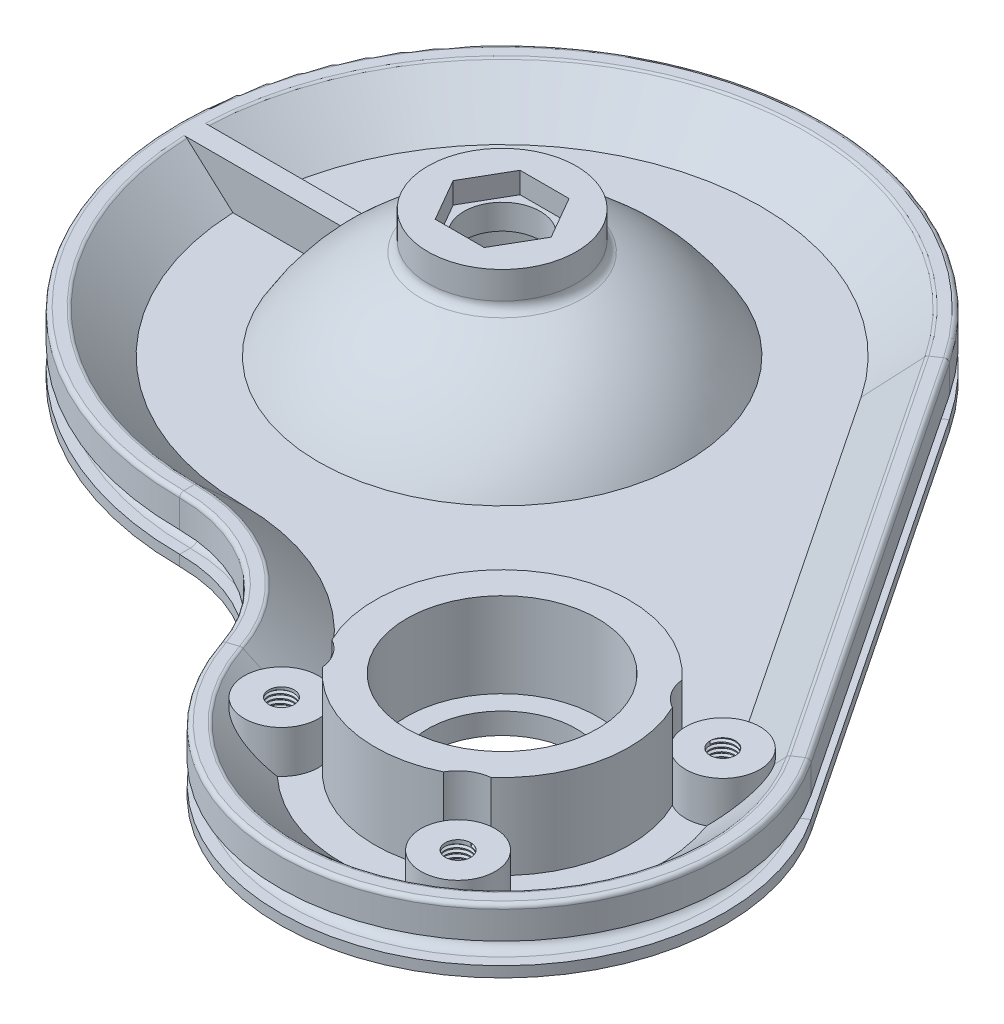
SolidWorks part; units mm, degrees
ref_plane "Front Plane" through (0, 0, 0) normal (0, 0, 1) x (1, 0, 0)
ref_plane "Top Plane" through (0, 0, 0) normal (0, 1, 0) x (1, 0, 0)
ref_plane "Right Plane" through (0, 0, 0) normal (1, 0, 0) x (0, 0, -1)
sketch "Sketch2" plane through (0, 0, 0) normal (0, 0, 1) x (1, 0, 0)
  line L0 (30, 0) -> (30, 13.541)
  line L1 (17.5, 28.5412) -> (17.5, 35)
  line L2 (17.5, 35) -> (0, 35)
  line L3 (0, 35) -> (0, 25)
  line L4 (30, 0) -> (45.8258, 0)
  arc A0 (30, 13.541) -> (0, 25) centre (0, -20) ccw
  arc A1 (45.8258, 0) -> (19.0476, 26.2297) centre (0, -20) ccw
  arc A2 (19.0476, 26.2297) -> (17.5, 28.5412) centre (20, 28.5412) cw
  dimension "D2" = 50
  dimension "D3" = 45
  dimension "D7" = 2.5
  dimension "D1" = 20
  dimension "D4" = 35
  dimension "D5" = 30
  dimension "D6" = 17.5
revolve "Revolve1" add sketch "Sketch2" angle 360 about L3
sketch "Sketch3" plane through (0, 0, 0) normal (0, 1, 0) x (1, 0, 0)
  line L0 (0, 124.3048) -> (0, -56.7221) construction
  line L1 (0, 0) -> (84.8528, -84.8528) construction
  line L2 (116.0487, -64.0426) -> (50.7453, 33.8513)
  line L3 (84.8528, -84.8528) -> (130.4614, -39.2442) construction
  arc A0 (0, -61) -> (50.7453, 33.8513) centre (0, 0) cw
  arc A1 (116.0487, -64.0426) -> (49.2416, -96.6042) centre (84.8528, -84.8528) cw
  arc A2 (49.2416, -96.6042) -> (0, -61) centre (0, -112.8534) ccw
  circle A3 centre (84.8528, -84.8528) radius 17.5
  circle A4 centre (0, 0) radius 30 construction
  circle A5 centre (0, 0) radius 30
  dimension "D2" = 61
  dimension "D3" = 37.5
  dimension "D5" = 35
  dimension "D1" = 120
  dimension "D4" = 45
extrude "Boss-Extrude1" add sketch "Sketch3" along normal blind 5
sketch "Sketch4" plane through (0, 0, 0) normal (0, 0, 1) x (1, 0, 0)
  line L0 (-61, 0) -> (-61, 5)
  line L1 (-61, 5) -> (-71.8312, 14.7435)
  line L2 (-72.5, 15) -> (-75, 15)
  line L3 (-76, 14) -> (-76, 7.5)
  line L4 (-61, 0) -> (-76, 0)
  line L5 (-76, 0) -> (-76, 2.5)
  line L6 (-76, 7.5) -> (-73.5, 7.5)
  line L7 (-76, 2.5) -> (-73.5, 2.5)
  arc A1 (-73.5, 2.5) -> (-73.5, 7.5) centre (-73.5, 5) ccw
  arc A2 (-71.8312, 14.7435) -> (-72.5, 15) centre (-72.5, 14) ccw
  arc A3 (-75, 15) -> (-76, 14) centre (-75, 14) ccw
  point P17 (-71.8563, 14.7227)
  dimension "D1" = 2.5
  dimension "D2" = 2.5
  dimension "D5" = 1
  dimension "D3" = 15
  dimension "D4" = 5
  dimension "D6" = 15
  dimension "D7" = 2.5
  dimension "D8" = 2.5
sketch "Sketch5" plane through (0, 5, 0) normal (0, 1, 0) x (1, 0, 0)
  line L1 (116.0487, -64.0426) -> (50.7453, 33.8513)
  line L2 (116.0487, -64.0426) -> (50.7453, 33.8513)
  arc A3 (50.7453, 33.8513) -> (0, -61) centre (0, 0) ccw
  arc A4 (49.2416, -96.6042) -> (0, -61) centre (0, -112.8534) ccw
  arc A5 (49.2416, -96.6042) -> (116.0487, -64.0426) centre (84.8528, -84.8528) ccw
  arc A6 (50.7453, 33.8513) -> (0, -61) centre (0, 0) ccw
  arc A7 (49.2416, -96.6042) -> (0, -61) centre (0, -112.8534) ccw
  arc A8 (49.2416, -96.6042) -> (116.0487, -64.0426) centre (84.8528, -84.8528) ccw
  dimension "D1" = 0
sweep "Sweep1" add profiles "Sketch4" path "Sketch5"
sketch "Sketch6" plane through (0, 5, 0) normal (0, 1, 0) x (1, 0, 0)
  circle A0 centre (84.8528, -84.8528) radius 22.5
  circle A1 centre (84.8528, -84.8528) radius 30
  dimension "D1" = 60
  dimension "D2" = 45
extrude "Boss-Extrude3" add sketch "Sketch6" along normal blind 20
sketch "Sketch7" plane through (0, 5, 0) normal (0, 1, 0) x (1, 0, 0)
  line L0 (84.8528, -84.8528) -> (163.9589, -32.0824) construction
  line L1 (116.0487, -64.0426) -> (50.7453, 33.8513) construction
  circle A0 centre (116.0487, -64.0426) radius 3
  circle A1 centre (116.0487, -64.0426) radius 8.75
  dimension "D2" = 17.5
  dimension "D3" = 6
  dimension "D1" = 90
extrude "Boss-Extrude4" add sketch "Sketch7" along normal blind 10
sketch "Sketch8" plane through (0, 15, 0) normal (0, 1, 0) x (1, 0, 0)
  circle A0 centre (116.0487, -64.0426) radius 3 construction
  circle A1 centre (116.0487, -64.0426) radius 3
extrude "Cut-Extrude1" cut sketch "Sketch8" against normal blind 30
thread "Thread1" pitch 1 method cut profile "Thread Profile1" start angle 0, offset 0, length 0, pitch 1, diameter 6
ref_plane "Plane1" through (113.0487, 15, 64.0426) normal (0, 0, 1) x (-1, 0, 0)
sketch "Thread Profile1" plane through (113.0487, 15, 64.0426) normal (0, 0, 1) x (-1, 0, 0)
  line L0 (0, 0) -> (0, 1) construction
  line L1 (0, 0) -> (0.5413, 0.3125)
  line L2 (0.5413, 0.3125) -> (0.5413, 0.4375)
  line L3 (0.5413, 0.4375) -> (0, 0.75)
  line L4 (0.5413, 0.375) -> (0, 0.375) construction
  line L11 (0, 0) -> (0, 0.75)
  point P2 (0, 0)
  dimension "Pitch" = 1
  dimension "Profile_Angle" = 60
  dimension "Profile_Land" = 0.125
  dimension "Profile_Height" = 0.5413
sketch "Sketch12" plane through (0, 15, 0) normal (0, 1, 0) x (1, 0, 0)
  arc A0 (111.8162, -71.7008) -> (107.3522, -65.009) centre (116.0487, -64.0426) cw
  circle A1 centre (84.8528, -84.8528) radius 30 construction
  arc A2 (107.3522, -65.009) -> (111.8162, -71.7008) centre (84.8528, -84.8528) ccw construction
  arc A3 (111.8162, -71.7008) -> (107.3522, -65.009) centre (84.8528, -84.8528) ccw
  arc A4 (111.8162, -71.7008) -> (107.3522, -65.009) centre (84.8528, -84.8528) ccw construction
  dimension "D1" = 8.75
extrude "Cut-Extrude2" cut sketch "Sketch12" along normal up to next
pattern_circular "CirPattern1" count 3 over 180 about axis through (84.8528, 5, 84.8528) along (0, 1, 0) of "Cut-Extrude2", "Thread1", "Cut-Extrude1", "Boss-Extrude4" reverse direction yes
sketch "Sketch13" plane through (0, 35, 0) normal (0, 1, 0) x (1, 0, 0)
  line L0 (-109.8638, 0) -> (106.0263, 0) construction
  line L1 (-11.547, 0) -> (-5.7735, -10)
  line L2 (-5.7735, -10) -> (5.7735, -10)
  line L3 (5.7735, -10) -> (11.547, 0)
  line L4 (11.547, 0) -> (5.7735, 10)
  line L5 (5.7735, 10) -> (-5.7735, 10)
  line L6 (-5.7735, 10) -> (-11.547, 0)
  circle A0 centre (0, 0) radius 10 construction
  dimension "D1" = 20
extrude "Cut-Extrude3" cut sketch "Sketch13" against normal blind 5
sketch "Sketch14" plane through (0, 30, 0) normal (0, 1, 0) x (1, 0, 0)
  circle A0 centre (0, 0) radius 9
  dimension "D1" = 18
extrude "Cut-Extrude4" cut sketch "Sketch14" against normal up to next
sketch "Sketch15" plane through (0, 15, 0) normal (0, 1, 0) x (1, 0, 0)
  line L0 (-75, 0) -> (-31.9967, 0)
rib "Rib1" sketch "Sketch15" sketch "Sketch15" thickness 5 extrusion direction normal to sketch draft on no parameters "D1"=5
